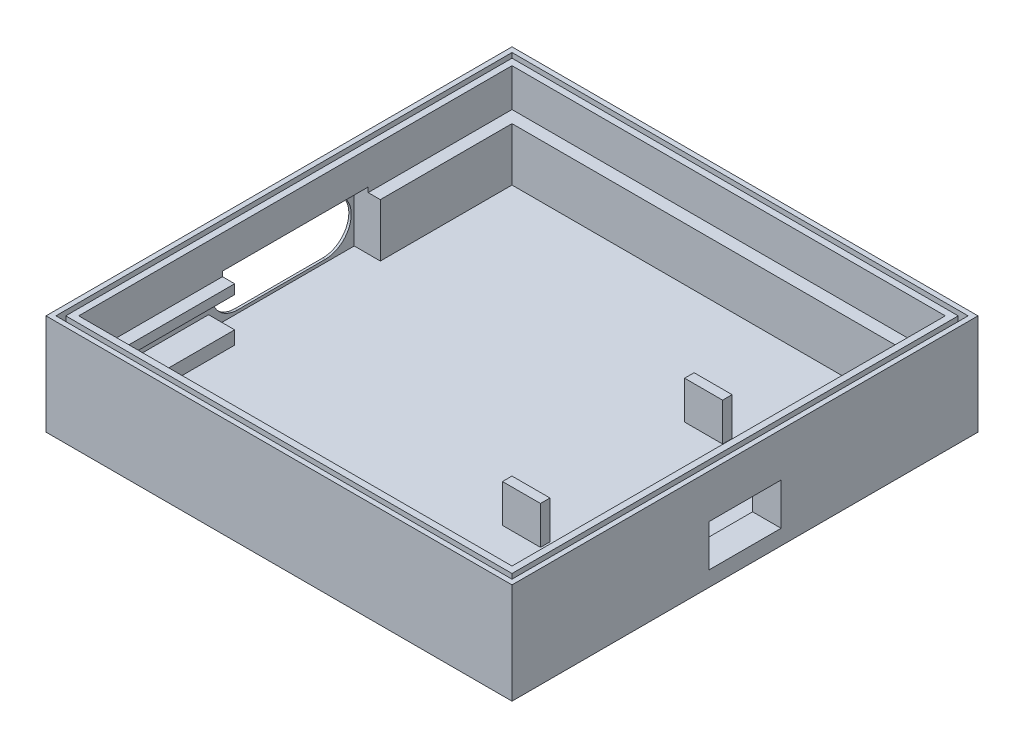
SolidWorks part; units mm, degrees
ref_plane "Front" through (0, 0, 0) normal (0, 0, 1) x (1, 0, 0)
ref_plane "Top" through (0, 0, 0) normal (0, 1, 0) x (1, 0, 0)
ref_plane "Right" through (0, 0, 0) normal (1, 0, 0) x (0, 0, -1)
sketch "Sketch2" plane through (0, 0, 0) normal (0, 1, 0) x (1, 0, 0)
  line L0 (0, -155.702) -> (0, 155.702)
  line L1 (-155.702, -155.702) -> (155.702, -155.702)
  line L2 (-155.702, -155.702) -> (-155.702, 155.702)
  line L3 (-155.702, 155.702) -> (155.702, 155.702)
  line L4 (155.702, -155.702) -> (155.702, 155.702)
  line L9 (-155.702, 0) -> (155.702, 0)
  line L11 (-152.4, 152.4) -> (152.4, 152.4)
  line L12 (-152.4, 152.4) -> (-152.4, -152.4)
  line L13 (-152.4, -152.4) -> (152.4, -152.4)
  line L14 (152.4, 152.4) -> (152.4, -152.4)
  line L15 (-152.4, 152.4) -> (152.4, -152.4) construction
  line L16 (-152.4, -152.4) -> (152.4, 152.4) construction
  line L17 (-149.098, 149.098) -> (149.098, 149.098)
  line L18 (-149.098, 149.098) -> (-149.098, -149.098)
  line L19 (-149.098, -149.098) -> (149.098, -149.098)
  line L20 (149.098, 149.098) -> (149.098, -149.098)
  line L21 (-149.098, 149.098) -> (149.098, -149.098) construction
  line L22 (-149.098, -149.098) -> (149.098, 149.098) construction
  line L23 (-144.78, 144.78) -> (144.78, 144.78)
  line L24 (-144.78, 144.78) -> (-144.78, -144.78)
  line L25 (-144.78, -144.78) -> (144.78, -144.78)
  line L26 (144.78, 144.78) -> (144.78, -144.78)
  line L27 (-144.78, 144.78) -> (144.78, -144.78) construction
  line L28 (-144.78, -144.78) -> (144.78, 144.78) construction
  line L29 (-136.652, -136.652) -> (136.652, -136.652)
  line L30 (-136.652, -136.652) -> (-136.652, 136.652)
  line L31 (-136.652, 136.652) -> (136.652, 136.652)
  line L32 (136.652, -136.652) -> (136.652, 136.652)
  line L33 (-136.652, -136.652) -> (136.652, 136.652) construction
  line L34 (-136.652, 136.652) -> (136.652, -136.652) construction
  point P8 (0, 0)
  point P13 (0, 0)
  point P18 (0, 0)
  point P25 (0, 0)
  dimension "D1" = 311.404
  dimension "D2" = 3.302
  dimension "D3" = 3.302
  dimension "D4" = 4.318
  dimension "D5" = 273.304
  dimension "D6" = 289.56
extrude "Boss-Extrude1" add sketch "Sketch2" along normal blind 67.31 contours L1 L4 L3 L2
sketch "Sketch4" plane through (0, 67.31, 0) normal (0, 1, 0) x (1, 0, 0)
  line L0 (-144.78, -144.78) -> (144.78, -144.78) construction
  line L1 (144.78, 144.78) -> (144.78, -144.78) construction
  line L2 (-144.78, 144.78) -> (144.78, 144.78) construction
  line L3 (-144.78, 144.78) -> (-144.78, -144.78) construction
  line L4 (-144.78, -144.78) -> (144.78, -144.78)
  line L5 (144.78, 144.78) -> (144.78, -144.78)
  line L6 (-144.78, 144.78) -> (144.78, 144.78)
  line L7 (-144.78, 144.78) -> (-144.78, -144.78)
extrude "Cut-Extrude1" cut sketch "Sketch4" against normal blind 25.4
sketch "Sketch5" plane through (0, 67.31, 0) normal (0, 1, 0) x (1, 0, 0)
  line L0 (-136.652, -136.652) -> (136.652, -136.652) construction
  line L1 (136.652, -136.652) -> (136.652, 136.652) construction
  line L2 (-136.652, 136.652) -> (136.652, 136.652) construction
  line L3 (-136.652, -136.652) -> (-136.652, 136.652) construction
  line L4 (-136.652, -136.652) -> (136.652, -136.652)
  line L5 (136.652, -136.652) -> (136.652, 136.652)
  line L6 (-136.652, 136.652) -> (136.652, 136.652)
  line L7 (-136.652, -136.652) -> (-136.652, 136.652)
extrude "Cut-Extrude2" cut sketch "Sketch5" against normal blind 60.96
sketch "Sketch6" plane through (0, 67.31, 0) normal (0, 1, 0) x (1, 0, 0)
  line L0 (-152.4, -152.4) -> (152.4, -152.4) construction
  line L1 (-149.098, -149.098) -> (149.098, -149.098) construction
  line L2 (152.4, 152.4) -> (152.4, -152.4) construction
  line L3 (149.098, 149.098) -> (149.098, -149.098) construction
  line L4 (-149.098, 149.098) -> (149.098, 149.098) construction
  line L5 (-152.4, 152.4) -> (152.4, 152.4) construction
  line L6 (-152.4, 152.4) -> (-152.4, -152.4) construction
  line L7 (-149.098, 149.098) -> (-149.098, -149.098) construction
  line L8 (-152.4, -152.4) -> (152.4, -152.4)
  line L9 (-149.098, -149.098) -> (149.098, -149.098)
  line L10 (152.4, 152.4) -> (152.4, -152.4)
  line L11 (149.098, 149.098) -> (149.098, -149.098)
  line L12 (-149.098, 149.098) -> (149.098, 149.098)
  line L13 (-152.4, 152.4) -> (152.4, 152.4)
  line L14 (-152.4, 152.4) -> (-152.4, -152.4)
  line L15 (-149.098, 149.098) -> (-149.098, -149.098)
extrude "Cut-Extrude3" cut sketch "Sketch6" against normal blind 12.7
sketch "Sketch7" plane through (-155.702, 0, 0) normal (-1, 0, 0) x (0, 0, 1)
  line L0 (-29.275, 25.75) -> (29.275, 25.75) construction
  line L1 (-29.275, 43.15) -> (29.275, 43.15)
  line L2 (-29.275, 8.35) -> (29.275, 8.35)
  line L3 (-46.675, 25.75) -> (46.675, 25.75) construction
  line L4 (136.652, 6.35) -> (-136.652, 6.35) construction
  arc A0 (-29.275, 43.15) -> (-29.275, 8.35) centre (-29.275, 25.75) ccw
  arc A1 (29.275, 8.35) -> (29.275, 43.15) centre (29.275, 25.75) ccw
  point P2 (0, 25.75)
  dimension "D1" = 34.8
  dimension "D2" = 93.35
  dimension "D3" = 2
extrude "Cut-Extrude4" cut sketch "Sketch7" against normal up to next
sketch "Sketch8" plane through (-136.652, 0, 0) normal (1, 0, 0) x (0, 0, -1)
  line L6 (29.275, 45.15) -> (48.675, 45.15)
  line L7 (48.675, 45.15) -> (48.675, 25.75)
  line L8 (-29.275, 6.35) -> (29.275, 6.35)
  line L9 (29.275, 45.15) -> (-29.275, 45.15)
  line L10 (-29.275, 6.35) -> (29.275, 6.35)
  line L11 (29.275, 45.15) -> (-29.275, 45.15)
  line L12 (48.675, 25.75) -> (48.675, 6.35)
  line L13 (48.675, 6.35) -> (29.275, 6.35)
  line L14 (-29.275, 45.15) -> (-48.675, 45.15)
  line L15 (-48.675, 45.15) -> (-48.675, 25.75)
  line L16 (-48.675, 25.75) -> (-48.675, 6.35)
  line L17 (-48.675, 6.35) -> (-29.275, 6.35)
  arc A9 (-29.275, 45.15) -> (-29.275, 6.35) centre (-29.275, 25.75) ccw
  arc A10 (29.275, 6.35) -> (29.275, 45.15) centre (29.275, 25.75) ccw
  arc A11 (-29.275, 45.15) -> (-29.275, 6.35) centre (-29.275, 25.75) ccw construction
  arc A12 (29.275, 6.35) -> (29.275, 45.15) centre (29.275, 25.75) ccw construction
  dimension "D1" = 2
extrude "Cut-Extrude5" cut sketch "Sketch8" against normal offset from surface (17.45 mm away) 1.6 up to face at (-155.702, 25.75, 0)
sketch "Sketch9" plane through (-155.702, 0, 0) normal (-1, 0, 0) x (0, 0, 1)
  line L5 (46.0141, 30.5) -> (48.175, 30.5)
  line L7 (46.0141, 21) -> (48.175, 21)
  line L8 (48.175, 30.5) -> (48.175, 21)
  arc A1 (29.275, 8.35) -> (29.275, 43.15) centre (29.275, 25.75) ccw construction
  arc A2 (29.275, 8.35) -> (29.275, 43.15) centre (29.275, 25.75) ccw construction
  arc A3 (46.0141, 30.5) -> (46.0141, 21) centre (29.275, 25.75) cw
  point P8 (46.675, 25.75)
  point P13 (48.175, 25.75)
  dimension "D1" = 1.5
  dimension "D2" = 9.5
extrude "Cut-Extrude6" cut sketch "Sketch9" against normal up to next
sketch "Sketch11" plane through (-136.652, 0, 0) normal (1, 0, 0) x (0, 0, -1)
  line L0 (-48.675, 41.91) -> (-48.675, 6.35) construction
  line L1 (-48.675, 35.56) -> (-124.875, 35.56)
  line L2 (-48.675, 35.56) -> (-48.675, 15.24)
  line L3 (-48.675, 15.24) -> (-124.875, 15.24)
  line L4 (-124.875, 35.56) -> (-124.875, 15.24)
  line L5 (-48.675, 41.91) -> (-144.78, 41.91) construction
  dimension "D1" = 6.35
  dimension "D2" = 76.2
  dimension "D3" = 20.32
extrude "Cut-Extrude7" cut sketch "Sketch11" against normal up to surface (17.45 mm away) up to face at (-154.102, 25.75, 0)
sketch "Sketch12" plane through (155.702, 0, 0) normal (1, 0, 0) x (0, 0, -1)
  line L5 (-144.78, 41.91) -> (144.78, 41.91) construction
  line L6 (24.13, 10.16) -> (-24.13, 10.16)
  line L11 (24.13, 10.16) -> (24.13, 38.1)
  line L12 (24.13, 38.1) -> (-24.13, 38.1)
  line L13 (-24.13, 10.16) -> (-24.13, 38.1)
  line L14 (24.13, 10.16) -> (-24.13, 38.1) construction
  line L15 (24.13, 38.1) -> (-24.13, 10.16) construction
  line L17 (-136.652, 6.35) -> (136.652, 6.35) construction
  line L18 (-136.652, 6.35) -> (136.652, 6.35)
  line L19 (-144.78, 41.91) -> (144.78, 41.91)
  line L20 (0, 41.91) -> (0, 6.35) construction
  point P0 (0, 24.13)
  point P5 (0, 24.7094)
  point P6 (0, 23.3895)
  point P7 (0, 27.6224)
  point P8 (0, 22.327)
  point P9 (0, 23.8377)
  point P10 (0, 23.7889)
  point P11 (0, 25.5158)
  point P19 (0, 24.4142)
  point P20 (0, 24.5687)
  point P21 (0, 0)
  point P22 (0, 0)
  point P23 (0, 0)
  point P24 (0, 23.9519)
  dimension "D1" = 27.94
  dimension "D2" = 48.26
  dimension "D3" = 3.81
extrude "Cut-Extrude8" cut sketch "Sketch12" against normal blind 19.05 and the other way through all contours L12 L13 L6 L11
sketch "Sketch13" plane through (0, 6.35, 0) normal (0, 1, 0) x (1, 0, 0)
  line L0 (58.1903, 63.5) -> (83.5903, 63.5)
  line L1 (57.1333, -57.15) -> (82.5333, -57.15)
  line L2 (57.1333, -57.15) -> (57.1333, -63.5)
  line L3 (57.1333, -63.5) -> (82.5333, -63.5)
  line L4 (82.5333, -57.15) -> (82.5333, -63.5)
  line L5 (57.1333, -57.15) -> (82.5333, -63.5) construction
  line L6 (57.1333, -63.5) -> (82.5333, -57.15) construction
  line L7 (-107.95, 57.15) -> (107.95, 57.15) construction
  line L8 (-107.95, 57.15) -> (-107.95, -57.15) construction
  line L9 (-107.95, -57.15) -> (107.95, -57.15) construction
  line L10 (107.95, 57.15) -> (107.95, -57.15) construction
  line L11 (-107.95, 57.15) -> (107.95, -57.15) construction
  line L12 (-107.95, -57.15) -> (107.95, 57.15) construction
  line L13 (58.1903, 63.5) -> (58.1903, 57.15)
  line L14 (58.1903, 57.15) -> (83.5903, 57.15)
  line L15 (83.5903, 63.5) -> (83.5903, 57.15)
  line L17 (-20.7617, 116.6646) -> (21.4174, 116.6646) construction
  line L18 (-20.7617, 116.6646) -> (-20.7617, 90.0176) construction
  line L19 (-20.7617, 90.0176) -> (21.4174, 90.0176) construction
  line L20 (21.4174, 116.6646) -> (21.4174, 90.0176) construction
  line L21 (-20.7617, 116.6646) -> (21.4174, 90.0176) construction
  line L22 (-20.7617, 90.0176) -> (21.4174, 116.6646) construction
  point P0 (69.8333, -60.325)
  point P5 (0, 0)
  point P9 (0, 0)
  point P21 (0.3279, 103.3411)
  dimension "D1" = 6.35
  dimension "D2" = 25.4
  dimension "D3" = 215.9
  dimension "D4" = 114.3
  dimension "D5" = 25.4
  dimension "D6" = 6.35
extrude "Boss-Extrude2" add sketch "Sketch13" along normal blind 25.4
sketch "Sketch14" plane through (0, 0, 0) normal (0, -1, 0) x (1, 0, 0)
  line L0 (-155.702, 155.702) -> (-155.702, -155.702) construction
  line L1 (-155.702, 155.702) -> (155.702, 155.702) construction
  circle A0 centre (-130.302, 130.302) radius 3.175
  dimension "D1" = 25.4
  dimension "D3" = 6.35
  dimension "D2" = 25.4
extrude "Cut-Extrude9" cut sketch "Sketch14" against normal blind 25.4
